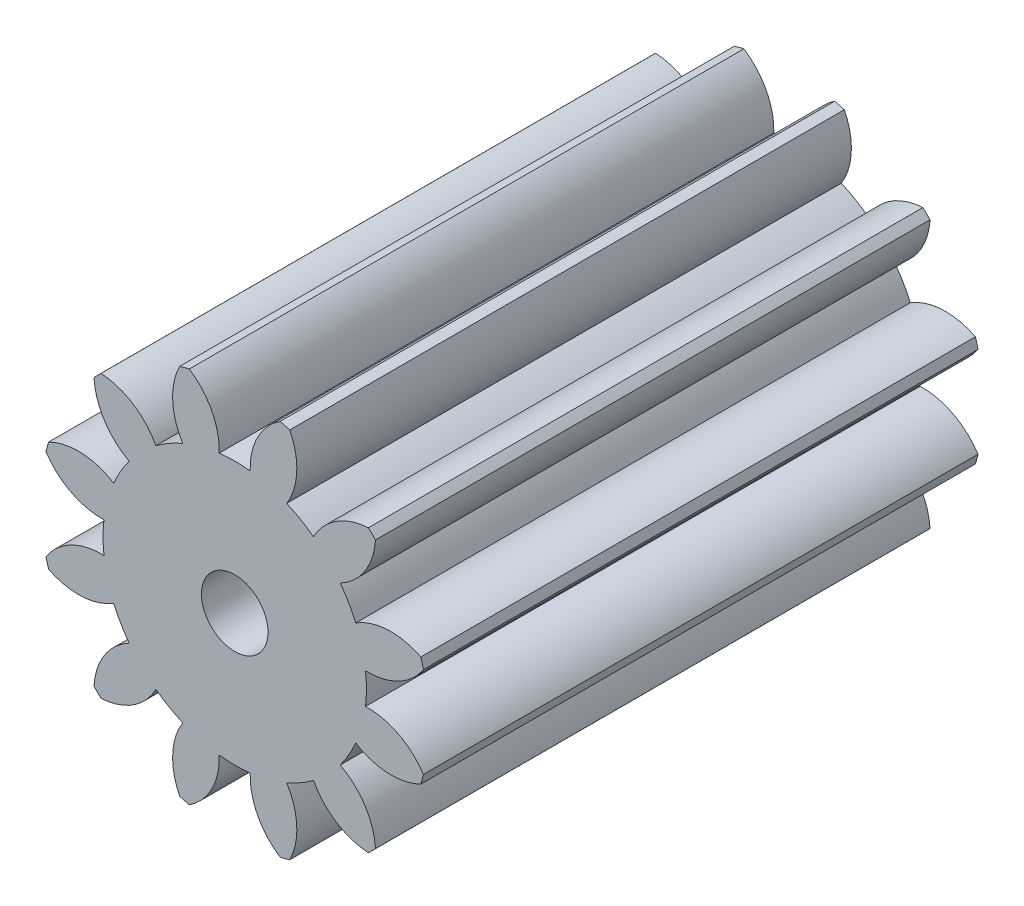
SolidWorks part; units mm, degrees
ref_plane "Front Plane" through (0, 0, 0) normal (0, 0, 1) x (1, 0, 0)
ref_plane "Top Plane" through (0, 0, 0) normal (0, 1, 0) x (1, 0, 0)
ref_plane "Right Plane" through (0, 0, 0) normal (1, 0, 0) x (0, 0, -1)
sketch "Sketch1" plane through (0, 0, 0) normal (0, 0, 1) x (1, 0, 0)
  circle A0 centre (0, 0) radius 3
  arc A48 (-12.6888, 12.0517) -> (-9.5148, 7.1035) centre (-6.699, 12.4017) ccw
  arc A49 (-9.5148, 7.1035) -> (-10.9092, 4.6884) centre (0, 0) ccw
  arc A50 (-10.9092, 4.6884) -> (-16.7815, 4.963) centre (-14.0897, -0.3993) ccw
  arc A51 (-16.7815, 4.963) -> (-17.0147, 4.0927) centre (0, 0) ccw
  arc A52 (-17.0147, 4.0927) -> (-11.7918, 1.3944) centre (-12.0024, 7.3907) ccw
  arc A53 (-11.7918, 1.3944) -> (-11.7918, -1.3944) centre (0, 0) ccw
  arc A54 (-11.7918, -1.3944) -> (-17.0147, -4.0927) centre (-12.0024, -7.3907) ccw
  arc A55 (-17.0147, -4.0927) -> (-16.7815, -4.963) centre (0, 0) ccw
  arc A56 (-16.7815, -4.963) -> (-10.9092, -4.6884) centre (-14.0897, 0.3993) ccw
  arc A57 (-10.9092, -4.6884) -> (-9.5148, -7.1035) centre (0, 0) ccw
  arc A58 (-9.5148, -7.1035) -> (-12.6888, -12.0517) centre (-6.699, -12.4017) ccw
  arc A59 (-12.6888, -12.0517) -> (-12.0517, -12.6888) centre (0, 0) ccw
  arc A60 (-12.0517, -12.6888) -> (-7.1035, -9.5148) centre (-12.4017, -6.699) ccw
  arc A61 (-7.1035, -9.5148) -> (-4.6884, -10.9092) centre (0, 0) ccw
  arc A62 (-4.6884, -10.9092) -> (-4.963, -16.7815) centre (0.3993, -14.0897) ccw
  arc A63 (-4.963, -16.7815) -> (-4.0927, -17.0147) centre (0, 0) ccw
  arc A64 (-4.0927, -17.0147) -> (-1.3944, -11.7918) centre (-7.3907, -12.0024) ccw
  arc A65 (-1.3944, -11.7918) -> (1.3944, -11.7918) centre (0, 0) ccw
  arc A66 (1.3944, -11.7918) -> (4.0927, -17.0147) centre (7.3907, -12.0024) ccw
  arc A67 (4.0927, -17.0147) -> (4.963, -16.7815) centre (0, 0) ccw
  arc A68 (4.963, -16.7815) -> (4.6884, -10.9092) centre (-0.3993, -14.0897) ccw
  arc A69 (4.6884, -10.9092) -> (7.1035, -9.5148) centre (0, 0) ccw
  arc A70 (7.1035, -9.5148) -> (12.0517, -12.6888) centre (12.4017, -6.699) ccw
  arc A71 (12.0517, -12.6888) -> (12.6888, -12.0517) centre (0, 0) ccw
  arc A72 (12.6888, -12.0517) -> (9.5148, -7.1035) centre (6.699, -12.4017) ccw
  arc A73 (9.5148, -7.1035) -> (10.9092, -4.6884) centre (0, 0) ccw
  arc A74 (10.9092, -4.6884) -> (16.7815, -4.963) centre (14.0897, 0.3993) ccw
  arc A75 (16.7815, -4.963) -> (17.0147, -4.0927) centre (0, 0) ccw
  arc A76 (17.0147, -4.0927) -> (11.7918, -1.3944) centre (12.0024, -7.3907) ccw
  arc A77 (11.7918, -1.3944) -> (11.7918, 1.3944) centre (0, 0) ccw
  arc A78 (11.7918, 1.3944) -> (17.0147, 4.0927) centre (12.0024, 7.3907) ccw
  arc A79 (17.0147, 4.0927) -> (16.7815, 4.963) centre (0, 0) ccw
  arc A80 (16.7815, 4.963) -> (10.9092, 4.6884) centre (14.0897, -0.3993) ccw
  arc A81 (10.9092, 4.6884) -> (9.5148, 7.1035) centre (0, 0) ccw
  arc A82 (9.5148, 7.1035) -> (12.6888, 12.0517) centre (6.699, 12.4017) ccw
  arc A83 (12.6888, 12.0517) -> (12.0517, 12.6888) centre (0, 0) ccw
  arc A84 (12.0517, 12.6888) -> (7.1035, 9.5148) centre (12.4017, 6.699) ccw
  arc A85 (7.1035, 9.5148) -> (4.6884, 10.9092) centre (0, 0) ccw
  arc A86 (4.6884, 10.9092) -> (4.963, 16.7815) centre (-0.3993, 14.0897) ccw
  arc A87 (4.963, 16.7815) -> (4.0927, 17.0147) centre (0, 0) ccw
  arc A88 (4.0927, 17.0147) -> (1.3944, 11.7918) centre (7.3907, 12.0024) ccw
  arc A89 (1.3944, 11.7918) -> (-1.3944, 11.7918) centre (0, 0) ccw
  arc A90 (-1.3944, 11.7918) -> (-4.0927, 17.0147) centre (-7.3907, 12.0024) ccw
  arc A91 (-4.0927, 17.0147) -> (-4.963, 16.7815) centre (0, 0) ccw
  arc A92 (-4.963, 16.7815) -> (-4.6884, 10.9092) centre (0.3993, 14.0897) ccw
  arc A93 (-4.6884, 10.9092) -> (-7.1035, 9.5148) centre (0, 0) ccw
  arc A94 (-7.1035, 9.5148) -> (-12.0517, 12.6888) centre (-12.4017, 6.699) ccw
  arc A95 (-12.0517, 12.6888) -> (-12.6888, 12.0517) centre (0, 0) ccw
  arc A96 (-12.6888, 12.0517) -> (-9.5148, 7.1035) centre (-6.699, 12.4017) ccw
  arc A97 (-9.5148, 7.1035) -> (-10.9092, 4.6884) centre (0, 0) ccw
  arc A98 (-10.9092, 4.6884) -> (-16.7815, 4.963) centre (-14.0897, -0.3993) ccw
  arc A99 (-16.7815, 4.963) -> (-17.0147, 4.0927) centre (0, 0) ccw
  arc A100 (-17.0147, 4.0927) -> (-11.7918, 1.3944) centre (-12.0024, 7.3907) ccw
  arc A101 (-11.7918, 1.3944) -> (-11.7918, -1.3944) centre (0, 0) ccw
  arc A102 (-11.7918, -1.3944) -> (-17.0147, -4.0927) centre (-12.0024, -7.3907) ccw
  arc A103 (-17.0147, -4.0927) -> (-16.7815, -4.963) centre (0, 0) ccw
  arc A104 (-16.7815, -4.963) -> (-10.9092, -4.6884) centre (-14.0897, 0.3993) ccw
  arc A105 (-10.9092, -4.6884) -> (-9.5148, -7.1035) centre (0, 0) ccw
  arc A106 (-9.5148, -7.1035) -> (-12.6888, -12.0517) centre (-6.699, -12.4017) ccw
  arc A107 (-12.6888, -12.0517) -> (-12.0517, -12.6888) centre (0, 0) ccw
  arc A108 (-12.0517, -12.6888) -> (-7.1035, -9.5148) centre (-12.4017, -6.699) ccw
  arc A109 (-7.1035, -9.5148) -> (-4.6884, -10.9092) centre (0, 0) ccw
  arc A110 (-4.6884, -10.9092) -> (-4.963, -16.7815) centre (0.3993, -14.0897) ccw
  arc A111 (-4.963, -16.7815) -> (-4.0927, -17.0147) centre (0, 0) ccw
  arc A112 (-4.0927, -17.0147) -> (-1.3944, -11.7918) centre (-7.3907, -12.0024) ccw
  arc A113 (-1.3944, -11.7918) -> (1.3944, -11.7918) centre (0, 0) ccw
  arc A114 (1.3944, -11.7918) -> (4.0927, -17.0147) centre (7.3907, -12.0024) ccw
  arc A115 (4.0927, -17.0147) -> (4.963, -16.7815) centre (0, 0) ccw
  arc A116 (4.963, -16.7815) -> (4.6884, -10.9092) centre (-0.3993, -14.0897) ccw
  arc A117 (4.6884, -10.9092) -> (7.1035, -9.5148) centre (0, 0) ccw
  arc A118 (7.1035, -9.5148) -> (12.0517, -12.6888) centre (12.4017, -6.699) ccw
  arc A119 (12.0517, -12.6888) -> (12.6888, -12.0517) centre (0, 0) ccw
  arc A120 (12.6888, -12.0517) -> (9.5148, -7.1035) centre (6.699, -12.4017) ccw
  arc A121 (9.5148, -7.1035) -> (10.9092, -4.6884) centre (0, 0) ccw
  arc A122 (10.9092, -4.6884) -> (16.7815, -4.963) centre (14.0897, 0.3993) ccw
  arc A123 (16.7815, -4.963) -> (17.0147, -4.0927) centre (0, 0) ccw
  arc A124 (17.0147, -4.0927) -> (11.7918, -1.3944) centre (12.0024, -7.3907) ccw
  arc A125 (11.7918, -1.3944) -> (11.7918, 1.3944) centre (0, 0) ccw
  arc A126 (11.7918, 1.3944) -> (17.0147, 4.0927) centre (12.0024, 7.3907) ccw
  arc A127 (17.0147, 4.0927) -> (16.7815, 4.963) centre (0, 0) ccw
  arc A128 (16.7815, 4.963) -> (10.9092, 4.6884) centre (14.0897, -0.3993) ccw
  arc A129 (10.9092, 4.6884) -> (9.5148, 7.1035) centre (0, 0) ccw
  arc A130 (9.5148, 7.1035) -> (12.6888, 12.0517) centre (6.699, 12.4017) ccw
  arc A131 (12.6888, 12.0517) -> (12.0517, 12.6888) centre (0, 0) ccw
  arc A132 (12.0517, 12.6888) -> (7.1035, 9.5148) centre (12.4017, 6.699) ccw
  arc A133 (7.1035, 9.5148) -> (4.6884, 10.9092) centre (0, 0) ccw
  arc A134 (4.6884, 10.9092) -> (4.963, 16.7815) centre (-0.3993, 14.0897) ccw
  arc A135 (4.963, 16.7815) -> (4.0927, 17.0147) centre (0, 0) ccw
  arc A136 (4.0927, 17.0147) -> (1.3944, 11.7918) centre (7.3907, 12.0024) ccw
  arc A137 (1.3944, 11.7918) -> (-1.3944, 11.7918) centre (0, 0) ccw
  arc A138 (-1.3944, 11.7918) -> (-4.0927, 17.0147) centre (-7.3907, 12.0024) ccw
  arc A139 (-4.0927, 17.0147) -> (-4.963, 16.7815) centre (0, 0) ccw
  arc A140 (-4.963, 16.7815) -> (-4.6884, 10.9092) centre (0.3993, 14.0897) ccw
  arc A141 (-4.6884, 10.9092) -> (-7.1035, 9.5148) centre (0, 0) ccw
  arc A142 (-7.1035, 9.5148) -> (-12.0517, 12.6888) centre (-12.4017, 6.699) ccw
  arc A143 (-12.0517, 12.6888) -> (-12.6888, 12.0517) centre (0, 0) ccw
  dimension "D1" = 0
extrude "Boss-Extrude1" add sketch "Sketch1" along normal blind 50 contours A0 | A96 A97 A98 A99 A100 A101 A102 A103 A104 A105 A106 A107 A108 A109 A110 A111 A112 A113 A114 A115 A116 A117 A118 A119 A120 A121 A122 A123 A124 A125 A126 A127 A128 A129 A130 A131 A132 A133 A134 A135 A136 A137 A138 A139 A140 A141 A142 A143 region at (0, 0, 0)
